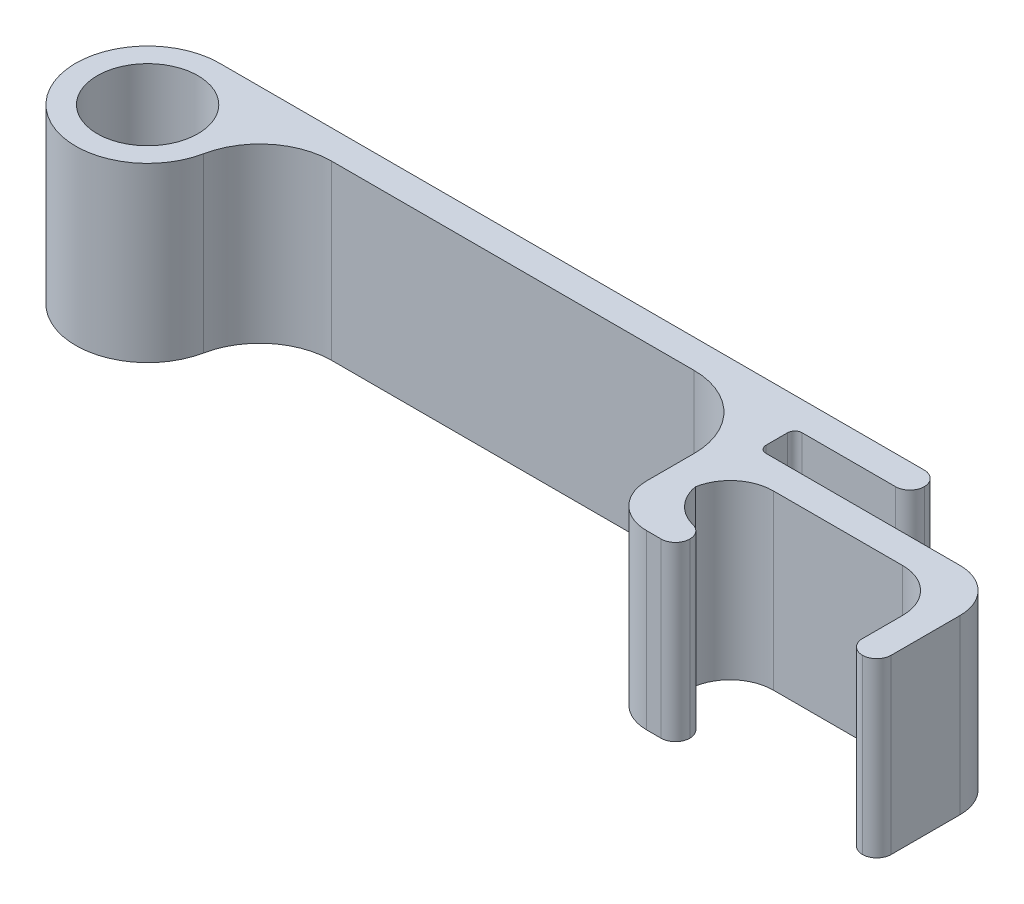
SolidWorks part; units mm, degrees
ref_plane "Front Plane" through (0, 0, 0) normal (0, 0, 1) x (1, 0, 0)
ref_plane "Top Plane" through (0, 0, 0) normal (0, 1, 0) x (1, 0, 0)
ref_plane "Right Plane" through (0, 0, 0) normal (1, 0, 0) x (0, 0, -1)
sketch "Sketch1" plane through (0, 0, 0) normal (0, 1, 0) x (1, 0, 0)
  circle A0 centre (0, 0) radius 5
  dimension "D1" = 10
extrude "Boss-Extrude1" add sketch "Sketch1" along normal blind 12
sketch "Sketch2" plane through (0, 12, 0) normal (0, 1, 0) x (1, 0, 0)
  circle A0 centre (0, 0) radius 3.5
  dimension "D1" = 7
extrude "Cut-Extrude1" cut sketch "Sketch2" against normal through all
sketch "Sketch3" plane through (0, 12, 0) normal (0, 1, 0) x (1, 0, 0)
  line L0 (0, 5) -> (50, 5)
  line L1 (50, 3) -> (4, 3)
  line L2 (50, 3) -> (50, 5)
  circle A0 centre (0, 0) radius 5 construction
  arc A2 (0, 5) -> (4, 3) centre (0, 0) cw
  dimension "D1" = 2
  dimension "D2" = 50
extrude "Boss-Extrude2" add sketch "Sketch3" against normal blind 12
sketch "Sketch4" plane through (0, 12, 0) normal (0, 1, 0) x (1, 0, 0)
  line L0 (40, 3) -> (40, -8.3)
  line L1 (4, 3) -> (50, 3) construction
  line L2 (50, 3) -> (50, 5) construction
  line L3 (50, 5) -> (0, 5) construction
  line L4 (40, -8.3) -> (45, -8.3)
  line L5 (45, -8.3) -> (45, -6.3)
  line L6 (45, -6.3) -> (42, -6.3)
  line L7 (42, -6.3) -> (42, 3)
  line L8 (42, 3) -> (40, 3)
  dimension "D1" = 10
  dimension "D2" = 13.3
  dimension "D3" = 5
  dimension "D4" = 2
  dimension "D5" = 2
extrude "Boss-Extrude3" add sketch "Sketch4" against normal blind 12
sketch "Sketch6" plane through (0, 12, 0) normal (0, 1, 0) x (1, 0, 0)
  line L0 (42, -6.3) -> (42, 3) construction
  line L1 (42, 0.5) -> (59, 0.5)
  line L2 (42, 0.5) -> (42, -1.5)
  line L3 (42, -1.5) -> (57, -1.5)
  line L4 (59, 0.5) -> (59, -1.5)
  line L5 (42, 3) -> (50, 3) construction
  line L7 (59, -1.5) -> (59, -8.3)
  line L8 (59, -8.3) -> (57, -8.3)
  line L9 (57, -8.3) -> (57, -1.5)
  dimension "D1" = 2
  dimension "D2" = 2.5
  dimension "D3" = 17
  dimension "D4" = 2
extrude "Boss-Extrude4" add sketch "Sketch6" against normal blind 12
fillet "Fillet1" radius 1 6 edges at (59, 6, 8.3) (57, 6, 8.3) (45, 6, 8.3) (45, 6, 6.3) (50, 6, -5) (50, 6, -3)
fillet "Fillet2" radius 3 5 edges at (57, 6, 1.5) (59, 6, -0.5) (40, 6, 8.3) (42, 6, 6.3) (42, 6, 1.5)
fillet "Fillet3" radius 5 1 edges at (40, 6, -3)
fillet "Fillet4" radius 5 1 edges at (4, 6, -3)
fillet "Fillet5" radius 0.5 2 edges at (42, 6, -0.5) (42, 6, -3)
sketch "Sketch7" plane through (0, 0, -5) normal (0, 0, -1) x (-1, 0, 0)
  text T0 "<b>Alex Fare</b>"
extrude "Cut-Extrude2" cut sketch "Sketch7" against normal blind 0.5
